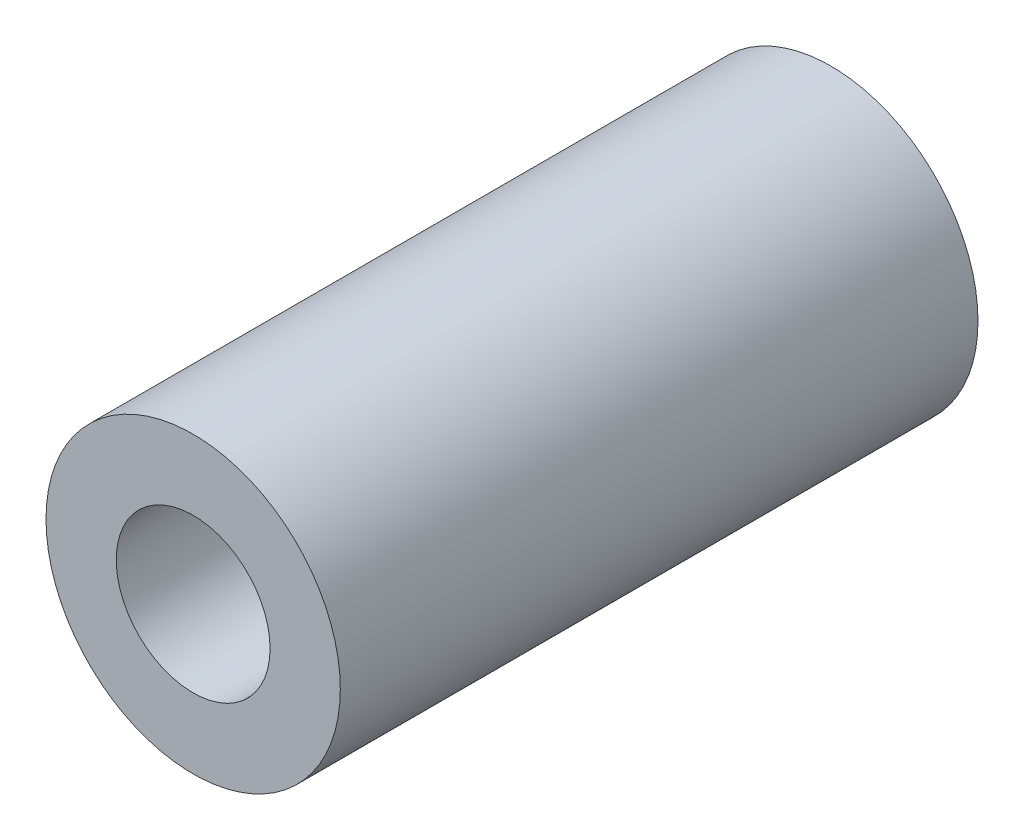
SolidWorks part; units mm, degrees
material "6061-T6 (SS)"
ref_plane "Front Plane" through (0, 0, 0) normal (0, 0, 1) x (1, 0, 0)
ref_plane "Top Plane" through (0, 0, 0) normal (0, 1, 0) x (1, 0, 0)
ref_plane "Right Plane" through (0, 0, 0) normal (1, 0, 0) x (0, 0, -1)
sketch "Sketch1" plane through (0, 0, 0) normal (0, 0, 1) x (1, 0, 0)
  circle A0 centre (0, 0) radius 4.7625
  circle A1 centre (0, 0) radius 2.4892
  dimension "D1" = 9.525
  dimension "D2" = 4.9784
extrude "Boss-Extrude1" add sketch "Sketch1" along normal mid plane 20.6375
